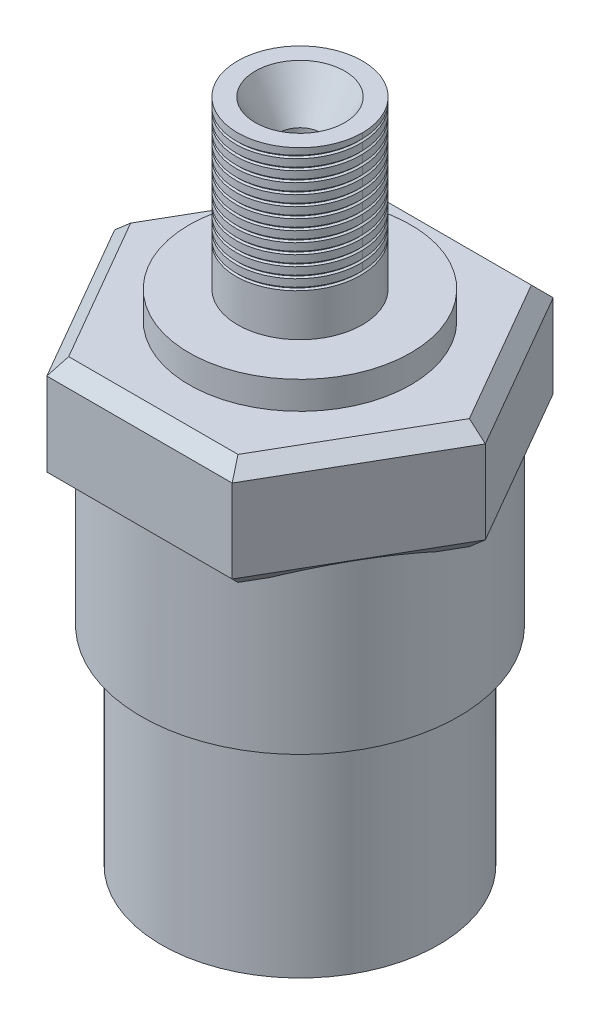
SolidWorks part; units mm, degrees
ref_plane "Front Plane" through (0, 0, 0) normal (0, 0, 1) x (1, 0, 0)
ref_plane "Top Plane" through (0, 0, 0) normal (0, 1, 0) x (1, 0, 0)
ref_plane "Right Plane" through (0, 0, 0) normal (1, 0, 0) x (0, 0, -1)
sketch "Sketch1" plane through (0, 0, 0) normal (0, 0, 1) x (1, 0, 0)
  line L0 (0, -338.4215) -> (0, 16582.6517) construction
  line L1 (-338.4215, 0) -> (16582.6517, 0) construction
  line L2 (0, 0) -> (10, 0)
  line L3 (10, 0) -> (10, 15)
  line L4 (10, 15) -> (11.455, 15)
  line L5 (11.455, 15) -> (11.455, 26)
  line L6 (11.455, 26) -> (0, 26)
  line L7 (0, 26) -> (0, 0)
  dimension "D1" = 10
  dimension "D2" = 15
  dimension "D3" = 11.455
  dimension "D4" = 26
revolve "Revolve1" add sketch "Sketch1" angle 360 about L7
sketch "Sketch2" plane through (0, 26, 0) normal (0, 1, 0) x (1, 0, 0)
  line L1 (6.6875, -11.5831) -> (13.375, 0)
  line L2 (13.375, 0) -> (6.6875, 11.5831)
  line L3 (6.6875, 11.5831) -> (-6.6875, 11.5831)
  line L4 (-6.6875, 11.5831) -> (-13.375, 0)
  line L5 (-13.375, 0) -> (-6.6875, -11.5831)
  line L6 (-6.6875, -11.5831) -> (6.6875, -11.5831)
  circle A0 centre (0, 0) radius 13.375 construction
  dimension "D1" = 26.75
extrude "Boss-Extrude1" add sketch "Sketch2" along normal blind 8
chamfer "Chamfer4" distance 1 angle 45 12 edges at (10.0312, 34, -5.7915) (10.0312, 34, 5.7915) (0, 34, 11.5831) (-10.0312, 34, 5.7915) (-10.0312, 34, -5.7915) (0, 34, -11.5831) (10.0312, 26, -5.7915) (10.0312, 26, 5.7915) (0, 26, 11.5831) (-10.0312, 26, 5.7915) (-10.0312, 26, -5.7915) (0, 26, -11.5831)
sketch "Sketch3" plane through (0, 0, 0) normal (0, 0, 1) x (1, 0, 0)
  line L0 (0, -1000) -> (0, 49000) construction
  line L1 (0, 34) -> (8, 34)
  line L2 (-6.1101, 34) -> (6.1101, 34) construction
  line L3 (6.1101, 34) -> (12.2203, 34) construction
  line L4 (8, 34) -> (8, 36)
  line L5 (8, 36) -> (4.5, 36)
  line L6 (4.5, 36) -> (4.5, 48)
  line L7 (4.5, 48) -> (0, 48)
  line L8 (0, 48) -> (0, 34)
  dimension "D1" = 8
  dimension "D2" = 4.5
  dimension "D3" = 2
  dimension "D4" = 12
revolve "Revolve2" add sketch "Sketch3" angle 360 about L0
thread "Thread1" pitch 0.25 method cut profile "Thread Profile1" start angle 0, offset 0, length 9, pitch 0.75, diameter 9
ref_plane "Plane1" through (-4.5, 48, 0) normal (0, 0, 1) x (-1, 0, 0)
sketch "Thread Profile1" plane through (-4.5, 48, 0) normal (0, 0, 1) x (-1, 0, 0)
  line L0 (0, 0) -> (0, 0.25) construction
  line L11 (0, 0) -> (0, 0.2187)
  line L12 (0, 0.2187) -> (-0.1353, 0.1406)
  line L13 (-0.1353, 0.1406) -> (-0.1353, 0.0781)
  line L15 (-0.1353, 0.0781) -> (0, 0)
  line L17 (-0.1353, 0.1094) -> (0, 0.1094) construction
  point P2 (0, 0)
  dimension "Pitch" = 0.25
  dimension "Profile_Angle" = 60
  dimension "Profile_Land" = 0.0625
  dimension "Profile_Height" = 0.1353
sketch "Sketch7" plane through (0, 0, 0) normal (0, 0, 1) x (1, 0, 0)
  line L0 (0, 0) -> (7, 0)
  line L1 (-10, 0) -> (10, 0) construction
  line L2 (7, 0) -> (7, 14)
  line L3 (7, 14) -> (4.5, 14)
  line L4 (4.5, 14) -> (4.5, 29)
  line L5 (4.5, 29) -> (1.5, 29)
  line L6 (1.5, 29) -> (1.5, 45.0092)
  line L7 (1.5, 45.0092) -> (3.2268, 48)
  line L8 (4.5, 48) -> (-4.5, 48) construction
  line L9 (0, 0) -> (0, 48)
  line L10 (0, 48) -> (3.2268, 48)
  spline S0 degree 2 poles (-4.5, 47.7813) (-4.5, 47.7344) (-3.182, 47.6875) (-1.864, 47.6406) (0, 47.5938) (1.864, 47.5469) (3.182, 47.5) (4.5, 47.4531) (4.5, 47.4063) (4.5, 47.3594) (3.182, 47.3125) (1.864, 47.2656) (0, 47.2188) (-1.864, 47.1719) (-3.182, 47.125) (-4.5, 47.0781) (-4.5, 47.0313) (-4.5, 46.9844) (-3.182, 46.9375) (-1.864, 46.8906) (0, 46.8438) (1.864, 46.7969) (3.182, 46.75) (4.5, 46.7031) (4.5, 46.6563) (4.5, 46.6094) (3.182, 46.5625) (1.864, 46.5156) (0, 46.4688) (-1.864, 46.4219) (-3.182, 46.375) (-4.5, 46.3281) (-4.5, 46.2813) (-4.5, 46.2344) (-3.182, 46.1875) (-1.864, 46.1406) (0, 46.0938) (1.864, 46.0469) (3.182, 46) (4.5, 45.9531) (4.5, 45.9063) (4.5, 45.8594) (3.182, 45.8125) (1.864, 45.7656) (0, 45.7188) (-1.864, 45.6719) (-3.182, 45.625) (-4.5, 45.5781) (-4.5, 45.5313) (-4.5, 45.4844) (-3.182, 45.4375) (-1.864, 45.3906) (0, 45.3438) (1.864, 45.2969) (3.182, 45.25) (4.5, 45.2031) (4.5, 45.1563) (4.5, 45.1094) (3.182, 45.0625) (1.864, 45.0156) (0, 44.9688) (-1.864, 44.9219) (-3.182, 44.875) (-4.5, 44.8281) (-4.5, 44.7813) (-4.5, 44.7344) (-3.182, 44.6875) (-1.864, 44.6406) (0, 44.5938) (1.864, 44.5469) (3.182, 44.5) (4.5, 44.4531) (4.5, 44.4063) (4.5, 44.3594) (3.182, 44.3125) (1.864, 44.2656) (0, 44.2188) (-1.864, 44.1719) (-3.182, 44.125) (-4.5, 44.0781) (-4.5, 44.0313) (-4.5, 43.9844) (-3.182, 43.9375) (-1.864, 43.8906) (0, 43.8438) (1.864, 43.7969) (3.182, 43.75) (4.5, 43.7031) (4.5, 43.6563) (4.5, 43.6094) (3.182, 43.5625) (1.864, 43.5156) (0, 43.4688) (-1.864, 43.4219) (-3.182, 43.375) (-4.5, 43.3281) (-4.5, 43.2813) (-4.5, 43.2344) (-3.182, 43.1875) (-1.864, 43.1406) (0, 43.0938) (1.864, 43.0469) (3.182, 43) (4.5, 42.9531) (4.5, 42.9063) (4.5, 42.8594) (3.182, 42.8125) (1.864, 42.7656) (0, 42.7188) (-1.864, 42.6719) (-3.182, 42.625) (-4.5, 42.5781) (-4.5, 42.5313) (-4.5, 42.4844) (-3.182, 42.4375) (-1.864, 42.3906) (0, 42.3438) (1.864, 42.2969) (3.182, 42.25) (4.5, 42.2031) (4.5, 42.1563) (4.5, 42.1094) (3.182, 42.0625) (1.864, 42.0156) (0, 41.9688) (-1.864, 41.9219) (-3.182, 41.875) (-4.5, 41.8281) (-4.5, 41.7813) (-4.5, 41.7344) (-3.182, 41.6875) (-1.864, 41.6406) (0, 41.5938) (1.864, 41.5469) (3.182, 41.5) (4.5, 41.4531) (4.5, 41.4063) (4.5, 41.3594) (3.182, 41.3125) (1.864, 41.2656) (0, 41.2188) (-1.864, 41.1719) (-3.182, 41.125) (-4.5, 41.0781) (-4.5, 41.0313) (-4.5, 40.9844) (-3.182, 40.9375) (-1.864, 40.8906) (0, 40.8438) (1.864, 40.7969) (3.182, 40.75) (4.5, 40.7031) (4.5, 40.6563) (4.5, 40.6094) (3.182, 40.5625) (1.864, 40.5156) (0, 40.4688) (-1.864, 40.4219) (-3.182, 40.375) (-4.5, 40.3281) (-4.5, 40.2813) (-4.5, 40.2344) (-3.182, 40.1875) (-1.864, 40.1406) (0, 40.0938) (1.864, 40.0469) (3.182, 40) (4.5, 39.9531) (4.5, 39.9063) (4.5, 39.8594) (3.182, 39.8125) (1.864, 39.7656) (0, 39.7188) (-1.864, 39.6719) (-3.182, 39.625) (-4.5, 39.5781) (-4.5, 39.5313) (-4.5, 39.4844) (-3.182, 39.4375) (-1.864, 39.3906) (0, 39.3438) (1.864, 39.2969) (3.182, 39.25) (4.5, 39.2031) (4.5, 39.1563) (4.5, 39.1094) (3.182, 39.0625) (1.864, 39.0156) (0, 38.9688) (-1.864, 38.9219) (-3.182, 38.875) (-4.5, 38.8281) (-4.5, 38.7813) knots 0 0 0 0.010417 0.010417 0.020833 0.020833 0.03125 0.03125 0.041667 0.041667 0.052083 0.052083 0.0625 0.0625 0.072917 0.072917 0.083333 0.083333 0.09375 0.09375 0.104167 0.104167 0.114583 0.114583 0.125 0.125 0.135417 0.135417 0.145833 0.145833 0.15625 0.15625 0.166667 0.166667 0.177083 0.177083 0.1875 0.1875 0.197917 0.197917 0.208333 0.208333 0.21875 0.21875 0.229167 0.229167 0.239583 0.239583 0.25 0.25 0.260417 0.260417 0.270833 0.270833 0.28125 0.28125 0.291667 0.291667 0.302083 0.302083 0.3125 0.3125 0.322917 0.322917 0.333333 0.333333 0.34375 0.34375 0.354167 0.354167 0.364583 0.364583 0.375 0.375 0.385417 0.385417 0.395833 0.395833 0.40625 0.40625 0.416667 0.416667 0.427083 0.427083 0.4375 0.4375 0.447917 0.447917 0.458333 0.458333 0.46875 0.46875 0.479167 0.479167 0.489583 0.489583 0.5 0.5 0.510417 0.510417 0.520833 0.520833 0.53125 0.53125 0.541667 0.541667 0.552083 0.552083 0.5625 0.5625 0.572917 0.572917 0.583333 0.583333 0.59375 0.59375 0.604167 0.604167 0.614583 0.614583 0.625 0.625 0.635417 0.635417 0.645833 0.645833 0.65625 0.65625 0.666667 0.666667 0.677083 0.677083 0.6875 0.6875 0.697917 0.697917 0.708333 0.708333 0.71875 0.71875 0.729167 0.729167 0.739583 0.739583 0.75 0.75 0.760417 0.760417 0.770833 0.770833 0.78125 0.78125 0.791667 0.791667 0.802083 0.802083 0.8125 0.8125 0.822917 0.822917 0.833333 0.833333 0.84375 0.84375 0.854167 0.854167 0.864583 0.864583 0.875 0.875 0.885417 0.885417 0.895833 0.895833 0.90625 0.90625 0.916667 0.916667 0.927083 0.927083 0.9375 0.9375 0.947917 0.947917 0.958333 0.958333 0.96875 0.96875 0.979167 0.979167 0.989583 0.989583 1 1 1 weights 1 0.92388 1 0.92388 1 0.92388 1 0.92388 1 0.92388 1 0.92388 1 0.92388 1 0.92388 1 0.92388 1 0.92388 1 0.92388 1 0.92388 1 0.92388 1 0.92388 1 0.92388 1 0.92388 1 0.92388 1 0.92388 1 0.92388 1 0.92388 1 0.92388 1 0.92388 1 0.92388 1 0.92388 1 0.92388 1 0.92388 1 0.92388 1 0.92388 1 0.92388 1 0.92388 1 0.92388 1 0.92388 1 0.92388 1 0.92388 1 0.92388 1 0.92388 1 0.92388 1 0.92388 1 0.92388 1 0.92388 1 0.92388 1 0.92388 1 0.92388 1 0.92388 1 0.92388 1 0.92388 1 0.92388 1 0.92388 1 0.92388 1 0.92388 1 0.92388 1 0.92388 1 0.92388 1 0.92388 1 0.92388 1 0.92388 1 0.92388 1 0.92388 1 0.92388 1 0.92388 1 0.92388 1 0.92388 1 0.92388 1 0.92388 1 0.92388 1 0.92388 1 0.92388 1 0.92388 1 0.92388 1 0.92388 1 0.92388 1 0.92388 1 0.92388 1 0.92388 1 0.92388 1 0.92388 1 0.92388 1 0.92388 1 0.92388 1 0.92388 1 0.92388 1 0.92388 1 0.92388 1 0.92388 1 0.92388 1 0.92388 1 0.92388 1 0.92388 1 0.92388 1 0.92388 1 0.92388 1 0.92388 1 0.92388 1 0.92388 1 0.92388 1 0.92388 1 construction
  dimension "D1" = 7
  dimension "D2" = 4.5
  dimension "D3" = 1.5
  dimension "D4" = 30
  dimension "D5" = 14
  dimension "D6" = 15
revolve "Cut-Revolve1" cut sketch "Sketch7" angle 360 about L9
